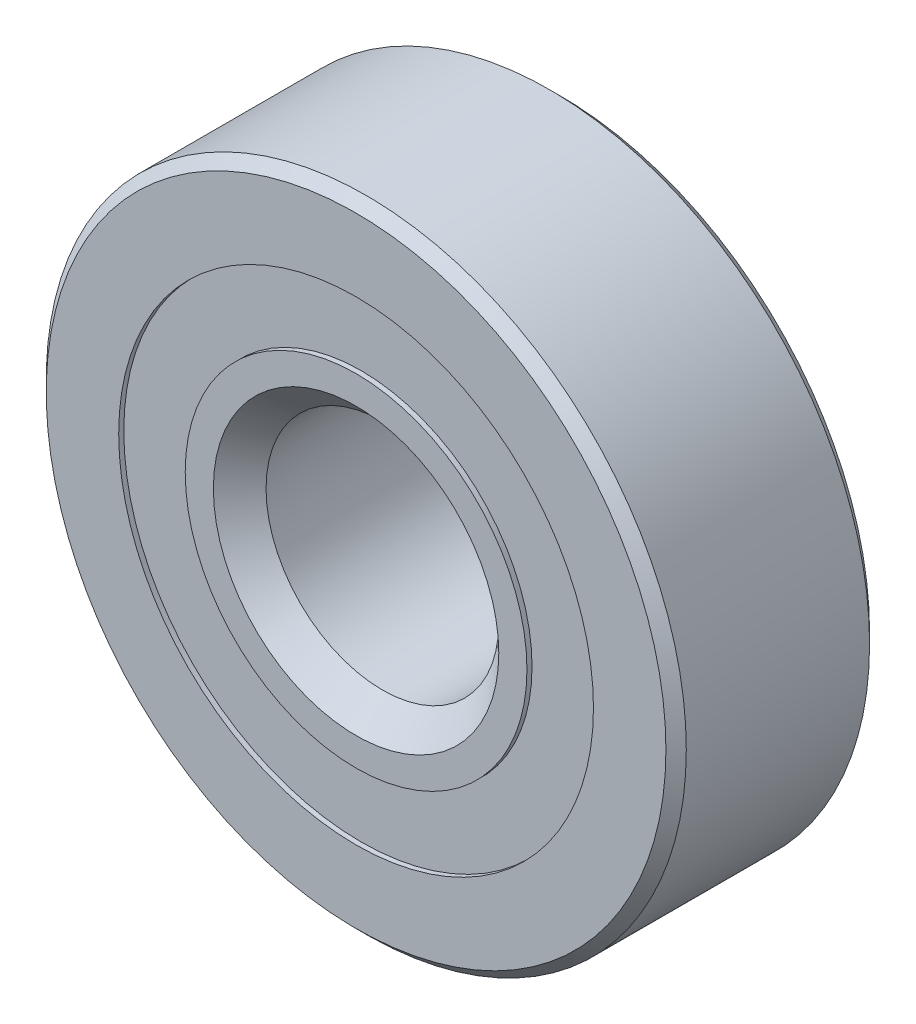
SolidWorks part; units mm, degrees
ref_plane "Front Plane" through (0, 0, 0) normal (0, 0, 1) x (1, 0, 0)
ref_plane "Top Plane" through (0, 0, 0) normal (0, 1, 0) x (1, 0, 0)
ref_plane "Right Plane" through (0, 0, 0) normal (1, 0, 0) x (0, 0, -1)
sketch "Sketch1" plane through (0, 0, 0) normal (1, 0, 0) x (0, 0, -1)
  line L0 (-5.5562, 0) -> (5.5562, 0) construction
  line L1 (0, 17.4625) -> (0, -17.4625) construction
  line L2 (5.0006, 17.4625) -> (-5.0006, 17.4625)
  line L3 (-5.0006, 17.4625) -> (-5.5563, 16.9069)
  line L4 (-5.5563, 16.9069) -> (-5.5563, 12.953)
  line L5 (-5.5563, 12.953) -> (-2.4694, 12.953)
  line L6 (5.5562, 12.953) -> (2.4694, 12.953)
  line L7 (5.5562, 16.9069) -> (5.5562, 12.953)
  line L8 (5.0006, 17.4625) -> (5.5562, 16.9069)
  line L9 (0, 17.4625) -> (0, 11.9062) construction
  line L10 (0, 11.9062) -> (0, 6.35) construction
  arc A0 (-2.4694, 12.953) -> (2.4694, 12.953) centre (0, 11.9062) cw
  point P14 (0, 6.35)
  dimension "Width" = 11.1125
  dimension "OD" = 34.925
  dimension "D1" = 45
  dimension "D2" = 0.5556
  dimension "D3" = 4.9389
  dimension "D4" = 1.0467
revolve "Revolve1" add sketch "Sketch1" angle 360 about L0
sketch "Sketch2" plane through (0, 0, 0) normal (1, 0, 0) x (0, 0, -1)
  line L0 (-5.2784, 10.8595) -> (-2.4694, 10.8595)
  line L1 (-5.5563, 16.9069) -> (-5.5563, -16.9069) construction
  line L2 (-5.5563, 9.3233) -> (-5.2784, 9.3233) construction
  line L3 (-5.2784, 9.0455) -> (-4.02, 7.7871)
  line L4 (-4.02, 7.7871) -> (0, 7.7871)
  line L5 (0, 17.4625) -> (0, -17.4625) construction
  line L6 (0, 7.7871) -> (0, 9.2241)
  line L7 (0, 9.2241) -> (0, 6.35) construction
  line L8 (-5.5563, 10.8595) -> (-5.5563, 7.7871) construction
  line L9 (-5.5563, 7.7871) -> (-4.02, 7.7871) construction
  line L10 (-5.2784, 10.8595) -> (-5.2784, 9.0455)
  line L11 (-5.2784, 10.8595) -> (-5.2784, 17.1847) construction
  line L12 (-5.0006, 17.4625) -> (-5.5563, 16.9069) construction
  arc A0 (-2.4694, 10.8595) -> (0, 9.2241) centre (0, 11.9062) ccw
  arc A1 (2.4694, 12.953) -> (-2.4694, 12.953) centre (0, 11.9062) ccw construction
  circle A2 centre (0, 11.9062) radius 2.6821 construction
  dimension "D1" = 45
revolve "Revolve2" [suppressed] add sketch "Sketch2" angle 360 about L0
sketch "Sketch3" plane through (0, 0, 0) normal (1, 0, 0) x (0, 0, -1)
  line L0 (-5.2784, 9.0455) -> (-4.02, 7.7871)
  line L1 (-4.02, 7.7871) -> (0, 7.7871)
  line L2 (0, 7.7871) -> (0, 9.2241)
  line L3 (-5.5563, 9.3233) -> (-5.5563, 7.7871)
  line L4 (-5.5563, 10.8595) -> (-5.5563, 7.7871) construction
  line L5 (-5.5563, 7.7871) -> (-4.1192, 6.35)
  line L6 (-4.1192, 6.35) -> (5.0006, 6.35)
  line L7 (5.0006, 17.4625) -> (5.0006, -17.4625) construction
  line L8 (5.0006, 6.35) -> (5.5562, 6.9056)
  line L9 (5.5562, -16.9069) -> (5.5562, 16.9069) construction
  line L10 (5.5562, 6.9056) -> (5.5562, 10.8595)
  line L11 (5.5562, 10.8595) -> (2.4694, 10.8595)
  line L12 (-5.5563, 9.3233) -> (-5.2784, 9.3233)
  line L13 (5.0006, 17.4625) -> (5.5562, 16.9069) construction
  line L14 (-5.2784, 9.3233) -> (-5.2784, 9.0455)
  circle A0 centre (0, 11.9062) radius 2.6821 construction
  arc A1 (2.4694, 10.8595) -> (0, 9.2241) centre (0, 11.9062) cw
revolve "Revolve3" add sketch "Sketch3" angle 360 about L0
sketch "Sketch4" plane through (0, 0, 0) normal (1, 0, 0) x (0, 0, -1)
  line L0 (-2.6821, 11.9062) -> (2.6821, 11.9062)
  circle A1 centre (0, 11.9062) radius 2.6821 construction
  arc A2 (-2.6821, 11.9062) -> (2.6821, 11.9062) centre (0, 11.9062) cw
  arc A3 (2.4694, 12.953) -> (-2.4694, 12.953) centre (0, 11.9062) ccw construction
revolve "Revolve4" add sketch "Sketch4" angle 360 about L0
ref_axis "Axis1" through (0, 0, -5.5562) along (0, 0, 1)
pattern_circular "CirPattern1" count 12 every 30 about axis through (0, 0, -5.5562) along (0, 0, 1) of bodies 104
sketch "Sketch5" plane through (0, 0, 0) normal (1, 0, 0) x (0, 0, -1)
  line L0 (-5.5563, 12.953) -> (-2.4694, 12.953) construction
  line L1 (-5.2784, 12.953) -> (-2.6821, 12.953)
  line L2 (-5.2784, 12.953) -> (-5.2784, 9.3233)
  line L3 (-5.2784, 9.3233) -> (-2.6821, 9.3233)
  line L4 (-2.6821, 12.953) -> (-2.6821, 9.3233)
  line L6 (-5.0006, 17.4625) -> (-5.5563, 16.9069) construction
  line L7 (0, 17.4625) -> (0, 6.35) construction
  line L8 (5.2784, 9.3233) -> (2.6821, 9.3233)
  line L9 (2.6821, 12.953) -> (2.6821, 9.3233)
  line L10 (5.2784, 12.953) -> (2.6821, 12.953)
  line L11 (5.2784, 12.953) -> (5.2784, 9.3233)
  circle A0 centre (0, 11.9062) radius 2.6821 construction
  point P10 (-5.2784, 17.1847)
revolve "Revolve5" add sketch "Sketch5" angle 360 about L0
equation "\"D2@Sketch1\" = \"Width@Sketch1\"*.05"
equation "\"D3@Sketch1\" = \"Width@Sketch1\"/2.25"
equation "\"D4@Sketch1\" = (((\"OD@Sketch1\"-\"Width@Sketch1\")/2)/3.25)/3.5"
equation "\"D2@CirPattern1\" = 360/\"Balls@CirPattern1\""
